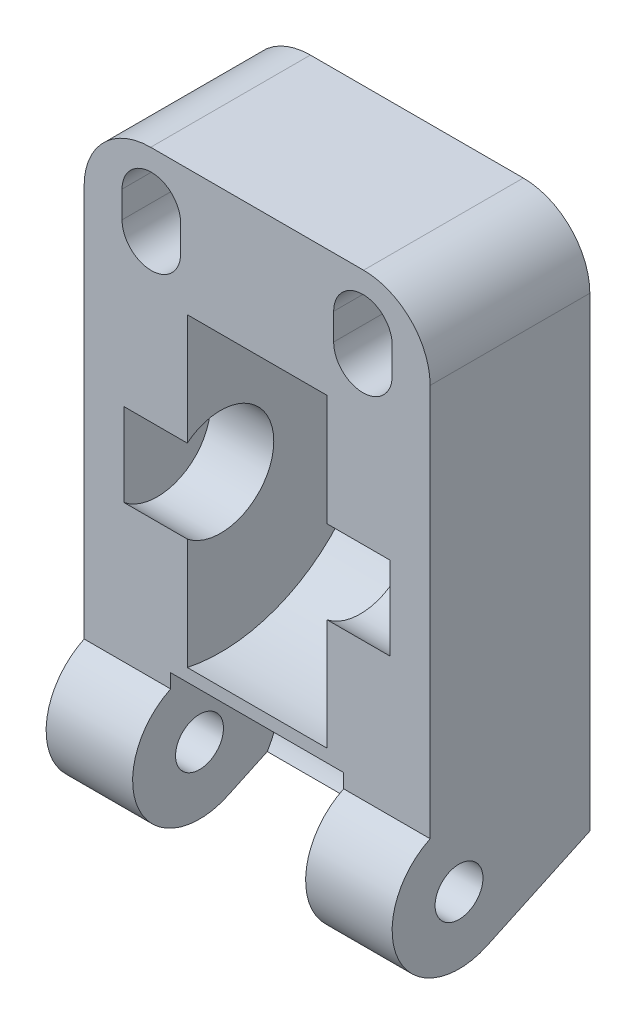
SolidWorks part; units mm, degrees
ref_plane "Front Plane" through (0, 0, 0) normal (0, 0, 1) x (1, 0, 0)
ref_plane "Top Plane" through (0, 0, 0) normal (0, 1, 0) x (1, 0, 0)
ref_plane "Right Plane" through (0, 0, 0) normal (1, 0, 0) x (0, 0, -1)
sketch "Sketch1" plane through (0, 0, 0) normal (1, 0, 0) x (0, 0, -1)
  line L0 (0, 0) -> (0, 40)
  line L1 (0, 0) -> (-7.7036, -3.5923)
  line L2 (0, 40) -> (-12, 40)
  line L5 (-12, 40) -> (-12, 5.5)
  arc A0 (-12, 5.5) -> (-7.7036, -3.5923) centre (-9.8286, 0.9648) ccw
  circle A1 centre (-9.8286, 0.9648) radius 1.8
  dimension "D8" = 3.6
  dimension "D1" = 8.5
  dimension "D2" = 40
  dimension "D3" = 115
  dimension "D4" = 34.5
  dimension "D5" = 12
extrude "Boss-Extrude1" add sketch "Sketch1" along normal mid plane 26
sketch "Sketch2" plane through (0, 0, 0) normal (1, 0, 0) x (0, 0, -1)
  line L0 (0, 19) -> (-9.5, 19) construction
  line L1 (0, 0) -> (0, 40) construction
  circle A0 centre (-9.5, 19) radius 4
  dimension "D2" = 8
  dimension "D1" = 9.5
  dimension "D3" = 19
extrude "Cut-Extrude1" cut sketch "Sketch2" against normal mid plane 20
sketch "Sketch3" plane through (0, 0, 0) normal (1, 0, 0) x (0, 0, -1)
  circle A0 centre (-9.5, 19) radius 11.75
  dimension "D1" = 23.5
extrude "Cut-Extrude2" cut sketch "Sketch3" against normal mid plane 10.5
sketch "Sketch4" plane through (0, 0, 0) normal (1, 0, 0) x (0, 0, -1)
  circle A0 centre (-9.8286, 0.9648) radius 6
  dimension "D1" = 12
extrude "Cut-Extrude3" cut sketch "Sketch4" against normal mid plane 13
sketch "Sketch7" plane through (0, 0, 0) normal (0, 0, -1) x (-1, 0, 0)
  line L0 (-7.95, 36.2) -> (-7.95, 34.2) construction
  line L1 (-5.75, 36.2) -> (-5.75, 34.2)
  line L2 (-10.15, 36.2) -> (-10.15, 34.2)
  line L3 (7.95, 36.2) -> (7.95, 34.2) construction
  line L4 (10.15, 36.2) -> (10.15, 34.2)
  line L5 (5.75, 36.2) -> (5.75, 34.2)
  line L6 (5.75, 35.2) -> (-5.75, 35.2) construction
  line L7 (0, 35.2) -> (0, 40) construction
  line L9 (-13, 40) -> (13, 40) construction
  line L10 (-13, 32) -> (13, 32) construction
  line L11 (-13, 0) -> (-13, 40) construction
  line L12 (13, 0) -> (13, 40) construction
  arc A0 (-5.75, 36.2) -> (-10.15, 36.2) centre (-7.95, 36.2) ccw
  arc A1 (-10.15, 34.2) -> (-5.75, 34.2) centre (-7.95, 34.2) ccw
  arc A2 (10.15, 36.2) -> (5.75, 36.2) centre (7.95, 36.2) ccw
  arc A3 (5.75, 34.2) -> (10.15, 34.2) centre (7.95, 34.2) ccw
  point P2 (-7.95, 35.2)
  point P7 (7.95, 35.2)
  dimension "D4" = 2.2
  dimension "D1" = 11.5
  dimension "D2" = 2
  dimension "D6" = 8
extrude "Cut-Extrude6" cut sketch "Sketch7" against normal through all
fillet "Fillet1" radius 5 2 edges at (-13, 40, 6) (13, 40, 6)
